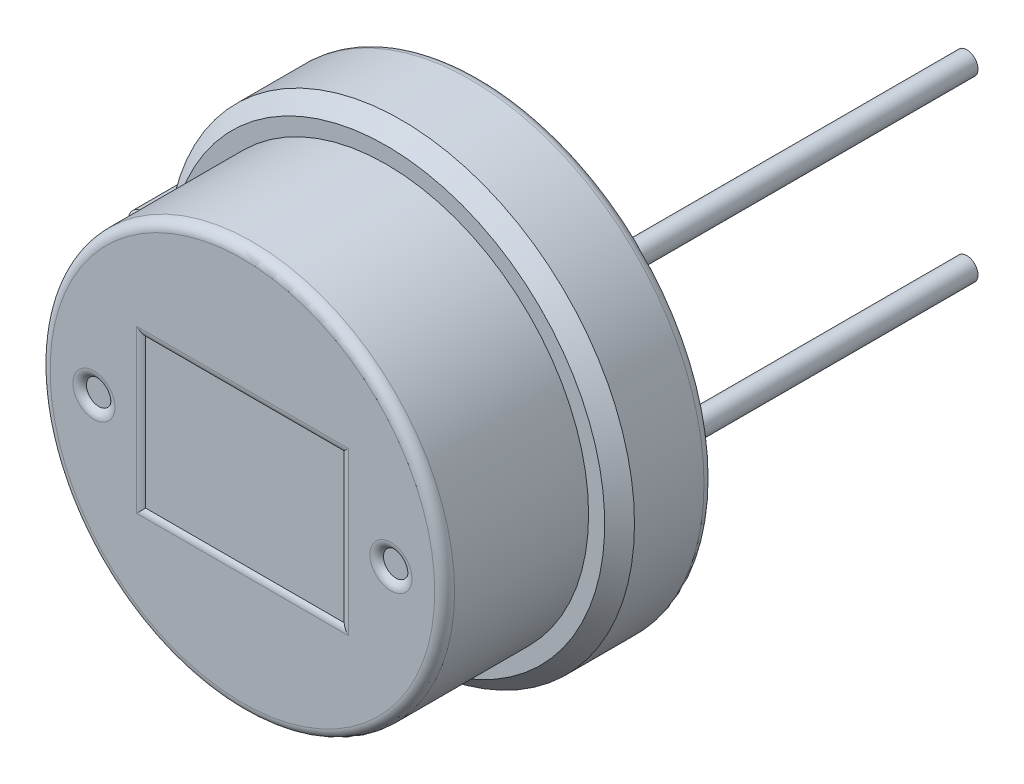
SolidWorks part; units mm, degrees
ref_plane "前视基准面" through (0, 0, 0) normal (0, 0, 1) x (1, 0, 0)
ref_plane "上视基准面" through (0, 0, 0) normal (0, 1, 0) x (1, 0, 0)
ref_plane "右视基准面" through (0, 0, 0) normal (1, 0, 0) x (0, 0, -1)
sketch "草图2" plane through (0, 0, 0) normal (0, 0, 1) x (1, 0, 0)
  line L0 (0, 6.1771) -> (0, -6.8536) construction
  line L1 (6.371, 0) -> (-6.6033, 0) construction
  line L2 (-5.5, 0.2) -> (-5.5, -0.2)
  line L3 (-5.2, -0.5) -> (-4.9356, -0.5)
  line L4 (-5.2, 0.5) -> (-4.9356, 0.5)
  arc A0 (-4.6394, -0.752) -> (-4.6394, 0.752) centre (0, 0) ccw
  arc A1 (-5.2, -0.5) -> (-5.5, -0.2) centre (-5.2, -0.2) cw
  arc A2 (-5.5, 0.2) -> (-5.2, 0.5) centre (-5.2, 0.2) cw
  arc A3 (-4.6394, -0.752) -> (-4.9356, -0.5) centre (-4.9356, -0.8) ccw
  arc A4 (-4.6394, 0.752) -> (-4.9356, 0.5) centre (-4.9356, 0.8) cw
  point P12 (-5.5, 0)
  point P14 (-5.5, -0.5)
  point P17 (-5.5, 0.5)
  point P19 (-4.6733, -0.5)
  point P22 (-4.6733, 0.5)
  dimension "D1" = 9.4
  dimension "D4" = 0.3
  dimension "D5" = 0.3
  dimension "D2" = 1
  dimension "D3" = 5.5
extrude "基座" add sketch "草图2" along normal blind 1.9
sketch "草图3" plane through (0, 0, 1.9) normal (0, 0, 1) x (1, 0, 0)
  circle A0 centre (0, 0) radius 4.075
  dimension "D1" = 8.15
extrude "封装体" add sketch "草图3" along normal blind 2.9
sketch "草图6" plane through (0, 0, 4.8) normal (0, 0, 1) x (1, 0, 0)
  line L1 (-2, 1.5) -> (2, 1.5)
  line L2 (-2, 1.5) -> (-2, -1.5)
  line L3 (-2, -1.5) -> (2, -1.5)
  line L4 (2, 1.5) -> (2, -1.5)
  line L5 (-2, 1.5) -> (2, -1.5) construction
  line L6 (-2, -1.5) -> (2, 1.5) construction
  point P0 (0, 0)
  dimension "D1" = 4
  dimension "D2" = 3
extrude "窗口" cut sketch "草图6" against normal blind 0.05
sketch "草图7" plane through (0, 0, 4.8) normal (0, 0, 1) x (1, 0, 0)
  line L0 (-6.0236, 0) -> (5.7873, 0) construction
  line L1 (0, 5.1414) -> (0, -5.3043) construction
  circle A4 centre (-2.9926, 0) radius 0.25
  circle A5 centre (2.9926, 0) radius 0.25
  dimension "D1" = 0.5
extrude "压点" cut sketch "草图7" against normal blind 0.1
sketch "草图4" plane through (0, 0, 0) normal (0, 0, -1) x (-1, 0, 0)
  line L0 (0, -4.9981) -> (0, 5.1357) construction
  line L1 (-5.2049, 0) -> (6.3427, 0) construction
  line L2 (0, 0) -> (-4.2904, -4.2904) construction
  line L3 (0, 0) -> (-1.7961, 1.7961) construction
  circle A0 centre (0, 0) radius 2.54 construction
  circle A1 centre (-1.7961, -1.7961) radius 0.225
  circle A2 centre (-1.7961, 1.7961) radius 0.225
  circle A7 centre (1.7961, -1.7961) radius 0.225
  dimension "D1" = 5.08
  dimension "D3" = 0.45
  dimension "D6" = 0.45
  dimension "D2" = 45
  dimension "D4" = 45
extrude "引脚" add sketch "草图4" along normal blind 8
chamfer "倒角1" distance 0.3 angle 45 8 edges at (-5.5, 0, 1.9) (-5.4121, -0.4121, 1.9) (-5.4121, 0.4121, 1.9) (-5.0678, -0.5, 1.9) (-5.0678, 0.5, 1.9) (-4.7412, -0.5715, 1.9) (-4.7412, 0.5715, 1.9) (4.7, 0, 1.9)
fillet "圆角1" radius 0.2 15 edges at (-4.7412, -0.5715, 0) (-5.0678, -0.5, 0) (-5.4121, -0.4121, 0) (-5.5, 0, 0) (-5.4121, 0.4121, 0) (-5.0678, 0.5, 0) (-4.7412, 0.5715, 0) (4.075, 0, 4.8) (4.7, 0, 0) (2.7426, 0, 4.8) (-2.7426, 0, 4.8) (0, 1.5, 4.8) (-2, 0, 4.8) (0, -1.5, 4.8) (2, 0, 4.8)
